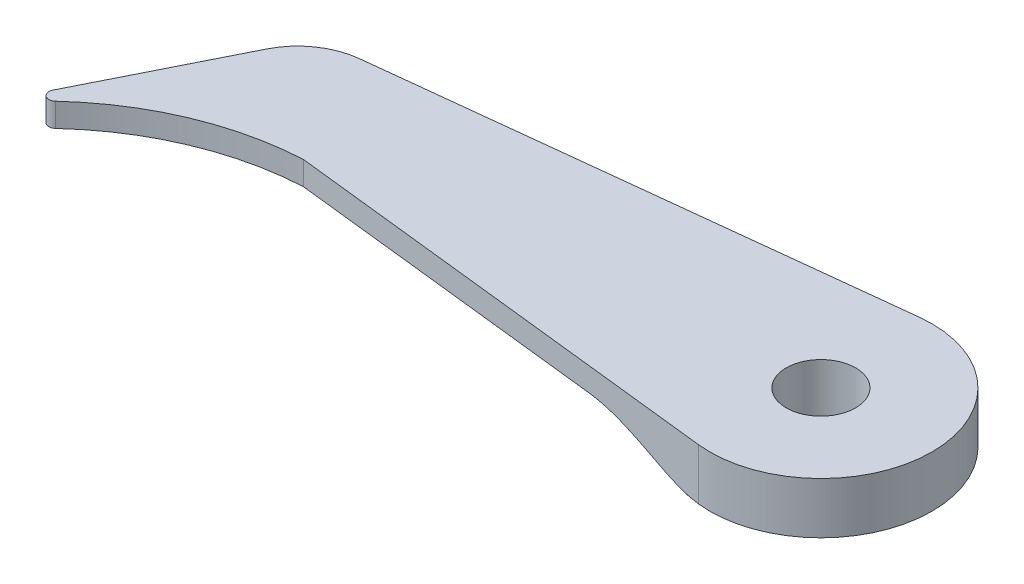
SolidWorks part; units mm, degrees
material "2014 Alloy"
ref_plane "Front Plane" through (0, 0, 0) normal (0, 0, 1) x (1, 0, 0)
ref_plane "Top Plane" through (0, 0, 0) normal (0, 1, 0) x (1, 0, 0)
ref_plane "Right Plane" through (0, 0, 0) normal (1, 0, 0) x (0, 0, -1)
sketch "Sketch2" plane through (0, 0, 0) normal (0, 1, 0) x (1, 0, 0)
  line L0 (-1.1238, 10.0977) -> (-50.6538, 4.5853)
  line L1 (-50.6538, 4.5853) -> (-60.8138, -15.7347)
  line L2 (-41.7638, -5.5747) -> (-1.1238, -10.0977)
  arc A1 (-60.8138, -15.7347) -> (-41.7638, -5.5747) centre (-40.4691, -30.9417) cw
  circle A2 centre (0, 0) radius 10.16
  dimension "D1" = 20.32
  dimension "D4" = 25.4
  dimension "D2" = 49.53
  dimension "D3" = 20.32
  dimension "D5" = 19.05
  dimension "D6" = 59.69
  dimension "D7" = 10.16
extrude "Boss-Extrude1" add sketch "Sketch2" against normal blind 4.699 contours A2 region at (0, 0, 0)
extrude "Boss-Extrude2" add sketch "Sketch2<3>" against normal blind 2.159 contours A2 L0 L1 A1 L2 region at (-29.6331, 0, 0.5694)
sketch "Sketch2<3>" plane through (0, 0, 0) normal (0, 1, 0) x (1, 0, 0) same geometry as "Sketch2"
sketch "Sketch3" plane through (0, -4.699, 0) normal (0, -1, 0) x (-1, 0, 0)
  circle A0 centre (0, 0) radius 3.175
  dimension "D1" = 6.35
extrude "Cut-Extrude1" cut sketch "Sketch3" against normal through all
fillet "Fillet1" radius 6.35 1 edges at (-10.16, -2.159, 0)
fillet "Fillet2" radius 0.635 1 edges at (-60.8138, -1.0795, 15.7347)
fillet "Fillet3" radius 6.35 1 edges at (-50.6538, -1.0795, -4.5853)
